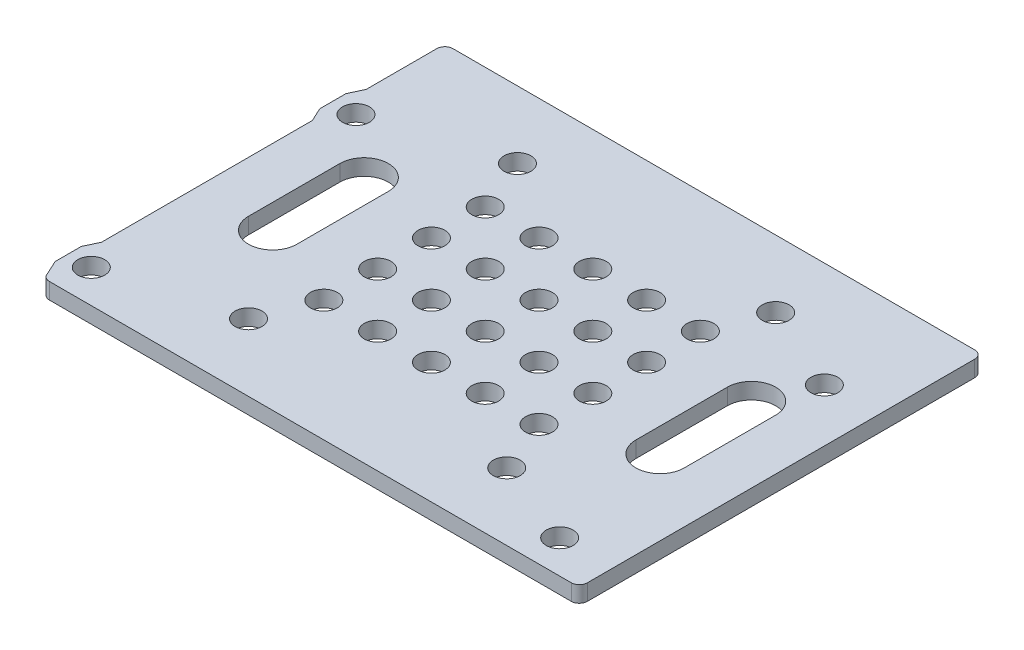
SolidWorks part; units mm, degrees
ref_plane "前视基准面" through (0, 0, 0) normal (0, 0, 1) x (1, 0, 0)
ref_plane "上视基准面" through (0, 0, 0) normal (0, 1, 0) x (1, 0, 0)
ref_plane "右视基准面" through (0, 0, 0) normal (1, 0, 0) x (0, 0, -1)
other "Configuration Table"
sketch "草图1" plane through (0, 0, 0) normal (0, 1, 0) x (1, 0, 0)
  line L1 (-50, 37.5) -> (50, 37.5)
  line L2 (-50, 37.5) -> (-50, -37.5)
  line L3 (-50, -37.5) -> (50, -37.5)
  line L4 (50, 37.5) -> (50, -37.5)
  line L5 (-50, 37.5) -> (50, -37.5) construction
  line L6 (-50, -37.5) -> (50, 37.5) construction
  point P0 (0, 0)
  dimension "D1" = 100
  dimension "D2" = 75
extrude "凸台-拉伸1" add sketch "草图1" along normal blind 3
sketch "草图2" plane through (0, 3, 0) normal (0, 1, 0) x (1, 0, 0)
  line L0 (-50, 37.5) -> (-50, -37.5) construction
  line L1 (40.184, -31.338) -> (-46.9, -31.338) construction
  line L2 (40.184, -31.338) -> (40.184, 17.87) construction
  line L3 (40.184, 17.87) -> (-46.9, 17.87) construction
  line L4 (-46.9, -31.338) -> (-46.9, 17.87) construction
  line L5 (40.184, -31.338) -> (-46.9, 17.87) construction
  line L6 (40.184, 17.87) -> (-46.9, -31.338) construction
  line L7 (-50, -37.5) -> (50, -37.5) construction
  line L9 (-3.358, 17.87) -> (-3.358, -31.338) construction
  line L10 (-46.9, -6.734) -> (40.184, -6.734) construction
  circle A0 centre (-46.9, 17.87) radius 2.5
  circle A1 centre (-46.9, -31.338) radius 2.5
  circle A2 centre (40.184, -31.338) radius 2.5
  circle A3 centre (40.184, 17.87) radius 2.5
  point P0 (-3.358, -6.734)
  dimension "D5" = 5
  dimension "D1" = 87.084
  dimension "D2" = 49.208
  dimension "D3" = 3.1
  dimension "D4" = 6.162
extrude "切除-拉伸1" cut sketch "草图2" against normal blind 3
sketch "草图3" plane through (0, 3, 0) normal (0, 1, 0) x (1, 0, 0)
  line L0 (0, 37.5) -> (0, -37.5) construction
  line L1 (50, 37.5) -> (-50, 37.5) construction
  line L2 (-50, -37.5) -> (50, -37.5) construction
  line L3 (-50, 0) -> (50, 0) construction
  line L4 (24, 25) -> (-24, 25) construction
  line L5 (24, 25) -> (24, -25) construction
  line L6 (24, -25) -> (-24, -25) construction
  line L7 (-24, 25) -> (-24, -25) construction
  line L8 (24, 25) -> (-24, -25) construction
  line L9 (24, -25) -> (-24, 25) construction
  line L10 (-50, 37.5) -> (-50, -37.5) construction
  line L11 (50, -37.5) -> (50, 37.5) construction
  line L12 (-36.0132, 8.5) -> (-36.0132, -8.5) construction
  line L13 (-31.5132, 8.5) -> (-31.5132, -8.5)
  line L14 (-40.5132, 8.5) -> (-40.5132, -8.5)
  line L15 (36.0132, 8.5) -> (36.0132, -8.5) construction
  line L16 (31.5132, 8.5) -> (31.5132, -8.5)
  line L17 (40.5132, 8.5) -> (40.5132, -8.5)
  circle A1 centre (-24, 25) radius 2.5
  circle A13 centre (24, 25) radius 2.5
  circle A14 centre (24, -25) radius 2.5
  circle A15 centre (-24, -25) radius 2.5
  circle A16 centre (0, 5) radius 2.5
  circle A17 centre (0, 15) radius 2.5
  circle A18 centre (0, -15) radius 2.5
  circle A19 centre (0, -5) radius 2.5
  circle A20 centre (10, 5) radius 2.5
  circle A21 centre (10, 15) radius 2.5
  circle A22 centre (10, -15) radius 2.5
  circle A23 centre (10, -5) radius 2.5
  circle A24 centre (20, 5) radius 2.5
  circle A25 centre (20, 15) radius 2.5
  circle A26 centre (20, -15) radius 2.5
  circle A27 centre (20, -5) radius 2.5
  circle A28 centre (-20, -5) radius 2.5
  circle A29 centre (-20, -15) radius 2.5
  circle A30 centre (-20, 15) radius 2.5
  circle A31 centre (-20, 5) radius 2.5
  circle A32 centre (-10, -5) radius 2.5
  circle A33 centre (-10, -15) radius 2.5
  circle A34 centre (-10, 15) radius 2.5
  circle A35 centre (-10, 5) radius 2.5
  arc A36 (-31.5132, 8.5) -> (-40.5132, 8.5) centre (-36.0132, 8.5) ccw
  arc A37 (-40.5132, -8.5) -> (-31.5132, -8.5) centre (-36.0132, -8.5) ccw
  arc A38 (31.5132, 8.5) -> (40.5132, 8.5) centre (36.0132, 8.5) cw
  arc A39 (40.5132, -8.5) -> (31.5132, -8.5) centre (36.0132, -8.5) cw
  point P62 (-36.0132, 0)
  point P71 (36.0132, 0)
  dimension "D1" = 5
  dimension "D2" = 5
  dimension "D7" = 17
  dimension "D8" = 4.5
  dimension "D3" = 50
  dimension "D5" = 5
  dimension "D6" = 3
  dimension "D4" = 48
extrude "切除-拉伸2" cut sketch "草图3" against normal blind 3
sketch "草图4" plane through (0, 3, 0) normal (0, 1, 0) x (1, 0, 0)
  line L0 (-50, 0) -> (50, 0) construction
  line L1 (-50, 37.5) -> (-50, -37.5) construction
  line L2 (50, -37.5) -> (50, 37.5) construction
  line L3 (-50, 22.87) -> (-51.2, 20.2966)
  line L4 (-51.2, 20.2966) -> (-51.2, 15.4434)
  line L5 (-51.2, 15.4434) -> (-50, 12.87)
  line L6 (-50, 12.87) -> (-50, 22.87)
  line L7 (-51.2, 17.87) -> (-50, 17.87) construction
  line L8 (-46.9, 17.87) -> (-50, 17.87) construction
  line L9 (-46.9, 17.87) -> (-46.9, -31.338) construction
  line L10 (-46.9, -6.734) -> (-50, -6.734) construction
  line L11 (-51.2, -28.9114) -> (-50, -26.338)
  line L12 (-51.2, -33.7646) -> (-51.2, -28.9114)
  line L13 (-50, -36.338) -> (-51.2, -33.7646)
  line L14 (-50, -26.338) -> (-50, -36.338)
  dimension "D1" = 1.2
  dimension "D2" = 25
  dimension "D3" = 10
extrude "凸台-拉伸2" add sketch "草图4" against normal blind 3
fillet "圆角1" radius 1.5 4 edges at (-50, 1.5, 37.5) (50, 1.5, 37.5) (50, 1.5, -37.5) (-50, 1.5, -37.5)
